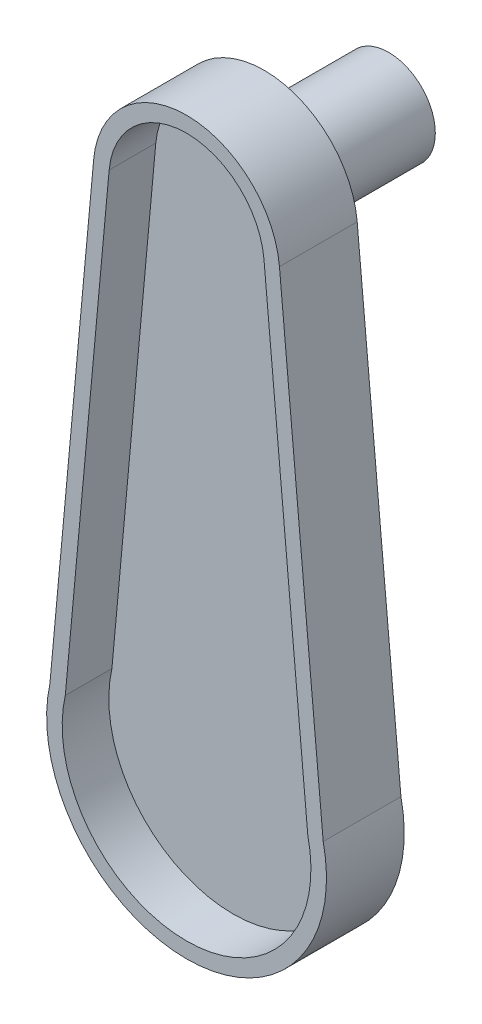
SolidWorks part; units mm, degrees
ref_plane "Front Plane" through (0, 0, 0) normal (0, 0, 1) x (1, 0, 0)
ref_plane "Top Plane" through (0, 0, 0) normal (0, 1, 0) x (1, 0, 0)
ref_plane "Right Plane" through (0, 0, 0) normal (1, 0, 0) x (0, 0, -1)
sketch "Sketch1" plane through (0, 0, 0) normal (0, 0, 1) x (1, 0, 0)
  line L0 (0, 0) -> (0, 16) construction
  line L1 (-3.9, 0.8888) -> (0, 0.8888) construction
  line L2 (-3.9, 0.8888) -> (-2.4895, 16.2289)
  line L3 (3.9, 0.8888) -> (2.4895, 16.2289)
  circle A0 centre (0, 0) radius 4 construction
  circle A1 centre (0, 16) radius 2.5 construction
  arc A2 (-2.4895, 16.2289) -> (2.4895, 16.2289) centre (0, 16) cw
  arc A3 (-3.9, 0.8888) -> (3.9, 0.8888) centre (0, 0) ccw
  point P5 (0, -4)
  point P6 (0, 18.5)
  point P7 (-3.9, 0.8888)
  dimension "D1" = 5
  dimension "D2" = 8
  dimension "D3" = 22.5
  dimension "D4" = 3.9
extrude "Boss-Extrude1" add sketch "Sketch1" along normal blind 1 contours L2 A2 L3 A3
extrude "Extrude-Thin1" add sketch "Sketch1<3>" along normal blind 2.5 thin thin type one direction wall 0.5
sketch "Sketch1<3>" plane through (0, 0, 0) normal (0, 0, 1) x (1, 0, 0) same geometry as "Sketch1"
sketch "Sketch2" plane through (0, 0, 0) normal (0, 0, -1) x (-1, 0, 0)
  circle A0 centre (0, 16) radius 1.5
  dimension "D1" = 3
extrude "Boss-Extrude2" add sketch "Sketch2" along normal blind 4
